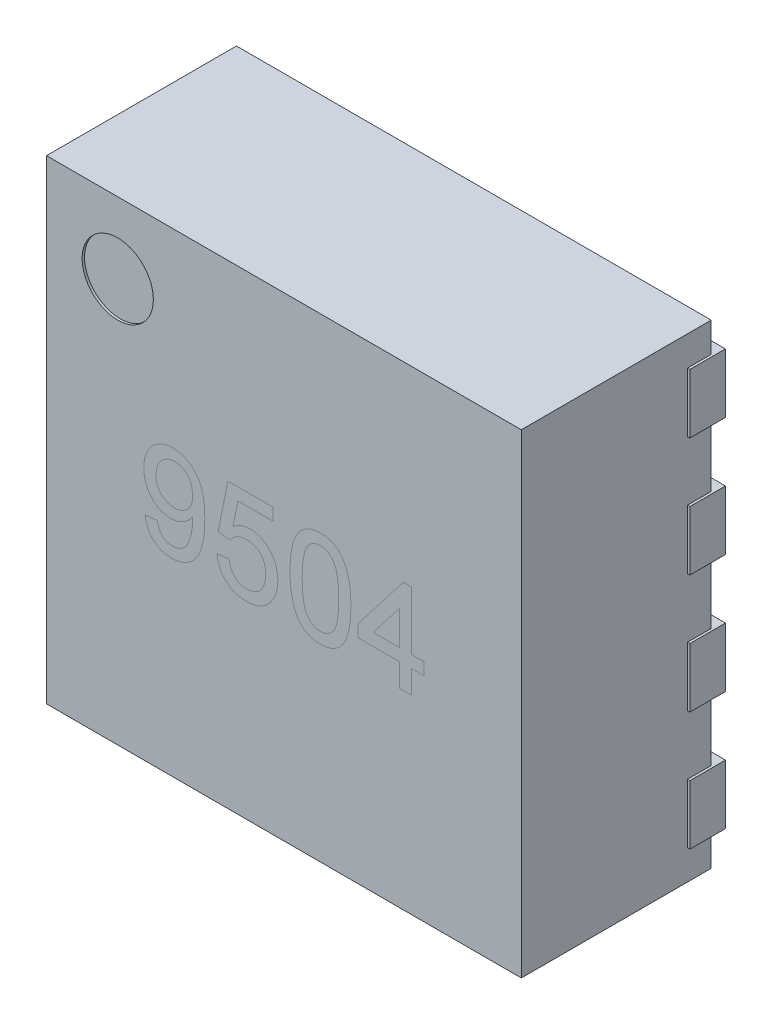
SolidWorks part; units mm, degrees
ref_plane "Спереди" through (0, 0, 0) normal (0, 0, 1) x (1, 0, 0)
ref_plane "Сверху" through (0, 0, 0) normal (0, 1, 0) x (1, 0, 0)
ref_plane "Справа" through (0, 0, 0) normal (1, 0, 0) x (0, 0, -1)
other "Configuration Table"
sketch "Sketch1" plane through (0, 0, 0) normal (0, 0, 1) x (1, 0, 0)
  line L1 (-1, 1) -> (1, 1)
  line L2 (-1, 1) -> (-1, -1)
  line L3 (-1, -1) -> (1, -1)
  line L4 (1, 1) -> (1, -1)
  line L5 (-1, 1) -> (1, -1) construction
  line L6 (-1, -1) -> (1, 1) construction
  point P0 (0, 0)
  dimension "D1" = 2
  dimension "D2" = 2
extrude "Boss-Extrude1" add sketch "Sketch1" along normal blind 0.8
sketch "Sketch3" plane through (0, 0, 0) normal (0, 0, -1) x (-1, 0, 0)
  line L0 (1, 1) -> (1, -1) construction
  line L1 (1.01, 0.875) -> (0.81, 0.875)
  line L2 (1.01, 0.875) -> (1.01, 0.625)
  line L3 (1.01, 0.625) -> (0.81, 0.625)
  line L4 (0.71, 0.775) -> (0.71, 0.725)
  line L5 (0.71, 0.75) -> (1.01, 0.75) construction
  line L6 (1.01, 0.375) -> (1.01, 0.125)
  line L7 (1.01, 0.375) -> (0.81, 0.375)
  line L8 (0.71, 0.275) -> (0.71, 0.225)
  line L9 (1.01, 0.125) -> (0.81, 0.125)
  line L10 (1.01, -0.125) -> (1.01, -0.375)
  line L11 (1.01, -0.125) -> (0.81, -0.125)
  line L12 (0.71, -0.225) -> (0.71, -0.275)
  line L13 (1.01, -0.375) -> (0.81, -0.375)
  line L14 (1.01, -0.625) -> (1.01, -0.875)
  line L15 (1.01, -0.625) -> (0.81, -0.625)
  line L16 (0.71, -0.725) -> (0.71, -0.775)
  line L17 (1.01, -0.875) -> (0.81, -0.875)
  line L18 (0, 1) -> (0, -1) construction
  line L19 (-1, 1) -> (1, 1) construction
  line L20 (1, -1) -> (-1, -1) construction
  line L21 (-0.71, 0.75) -> (-1.01, 0.75) construction
  line L22 (-1.01, -0.875) -> (-0.81, -0.875)
  line L23 (-0.71, -0.725) -> (-0.71, -0.775)
  line L24 (-1.01, -0.625) -> (-0.81, -0.625)
  line L25 (-1.01, -0.625) -> (-1.01, -0.875)
  line L26 (-1.01, -0.375) -> (-0.81, -0.375)
  line L27 (-0.71, -0.225) -> (-0.71, -0.275)
  line L28 (-1.01, -0.125) -> (-0.81, -0.125)
  line L29 (-1.01, -0.125) -> (-1.01, -0.375)
  line L30 (-1.01, 0.125) -> (-0.81, 0.125)
  line L31 (-0.71, 0.275) -> (-0.71, 0.225)
  line L32 (-1.01, 0.375) -> (-0.81, 0.375)
  line L33 (-1.01, 0.375) -> (-1.01, 0.125)
  line L34 (-0.71, 0.775) -> (-0.71, 0.725)
  line L35 (-1.01, 0.625) -> (-0.81, 0.625)
  line L36 (-1.01, 0.875) -> (-1.01, 0.625)
  line L37 (-1.01, 0.875) -> (-0.81, 0.875)
  arc A0 (0.81, 0.625) -> (0.71, 0.725) centre (0.81, 0.725) cw
  arc A1 (0.81, 0.875) -> (0.71, 0.775) centre (0.81, 0.775) ccw
  arc A2 (0.81, 0.375) -> (0.71, 0.275) centre (0.81, 0.275) ccw
  arc A3 (0.81, 0.125) -> (0.71, 0.225) centre (0.81, 0.225) cw
  arc A4 (0.81, -0.125) -> (0.71, -0.225) centre (0.81, -0.225) ccw
  arc A5 (0.81, -0.375) -> (0.71, -0.275) centre (0.81, -0.275) cw
  arc A6 (0.81, -0.625) -> (0.71, -0.725) centre (0.81, -0.725) ccw
  arc A7 (0.81, -0.875) -> (0.71, -0.775) centre (0.81, -0.775) cw
  arc A8 (-0.81, -0.875) -> (-0.71, -0.775) centre (-0.81, -0.775) ccw
  arc A9 (-0.81, -0.625) -> (-0.71, -0.725) centre (-0.81, -0.725) cw
  arc A10 (-0.81, -0.375) -> (-0.71, -0.275) centre (-0.81, -0.275) ccw
  arc A11 (-0.81, -0.125) -> (-0.71, -0.225) centre (-0.81, -0.225) cw
  arc A12 (-0.81, 0.125) -> (-0.71, 0.225) centre (-0.81, 0.225) ccw
  arc A13 (-0.81, 0.375) -> (-0.71, 0.275) centre (-0.81, 0.275) cw
  arc A14 (-0.81, 0.875) -> (-0.71, 0.775) centre (-0.81, 0.775) cw
  arc A15 (-0.81, 0.625) -> (-0.71, 0.725) centre (-0.81, 0.725) ccw
  point P6 (1.01, 0.75)
  dimension "D5" = 0.1
  dimension "D1" = 0.25
  dimension "D2" = 0.01
  dimension "D3" = 0.3
  dimension "D4" = 0.75
  dimension "D6" = 4
extrude "Boss-Extrude2" add sketch "Sketch3" along normal blind 0.05
sketch "Sketch4" plane through (0, 0, 0) normal (0, 0, -1) x (-1, 0, 0)
  line L4 (1.01, 0.875) -> (0.81, 0.875)
  line L5 (0.71, 0.775) -> (0.71, 0.725)
  line L6 (0.81, 0.625) -> (1.01, 0.625)
  line L7 (1.01, 0.625) -> (1.01, 0.875)
  line L8 (1.01, 0.875) -> (0.81, 0.875)
  line L9 (0.71, 0.775) -> (0.71, 0.725)
  line L10 (0.81, 0.625) -> (1.01, 0.625)
  line L11 (1.01, 0.625) -> (1.01, 0.875)
  line L12 (1.01, -0.375) -> (1.01, -0.125)
  line L13 (0.81, -0.375) -> (1.01, -0.375)
  line L14 (0.71, -0.225) -> (0.71, -0.275)
  line L15 (1.01, -0.125) -> (0.81, -0.125)
  line L16 (1.01, -0.375) -> (1.01, -0.125)
  line L17 (0.81, -0.375) -> (1.01, -0.375)
  line L18 (0.71, -0.225) -> (0.71, -0.275)
  line L19 (1.01, -0.125) -> (0.81, -0.125)
  line L20 (1.01, 0.125) -> (1.01, 0.375)
  line L21 (1.01, 0.375) -> (0.81, 0.375)
  line L22 (0.71, 0.275) -> (0.71, 0.225)
  line L23 (0.81, 0.125) -> (1.01, 0.125)
  line L24 (1.01, 0.125) -> (1.01, 0.375)
  line L25 (1.01, 0.375) -> (0.81, 0.375)
  line L26 (0.71, 0.275) -> (0.71, 0.225)
  line L27 (0.81, 0.125) -> (1.01, 0.125)
  line L28 (1.01, -0.875) -> (1.01, -0.625)
  line L29 (1.01, -0.625) -> (0.81, -0.625)
  line L30 (0.71, -0.725) -> (0.71, -0.775)
  line L31 (0.81, -0.875) -> (1.01, -0.875)
  line L32 (1.01, -0.875) -> (1.01, -0.625)
  line L33 (1.01, -0.625) -> (0.81, -0.625)
  line L34 (0.71, -0.725) -> (0.71, -0.775)
  line L35 (0.81, -0.875) -> (1.01, -0.875)
  line L36 (-0.71, 0.725) -> (-0.71, 0.775)
  line L37 (-1.01, 0.625) -> (-0.81, 0.625)
  line L38 (-1.01, 0.875) -> (-1.01, 0.625)
  line L39 (-0.81, 0.875) -> (-1.01, 0.875)
  line L40 (-0.71, 0.725) -> (-0.71, 0.775)
  line L41 (-1.01, 0.625) -> (-0.81, 0.625)
  line L42 (-1.01, 0.875) -> (-1.01, 0.625)
  line L43 (-0.81, 0.875) -> (-1.01, 0.875)
  line L44 (-1.01, 0.125) -> (-0.81, 0.125)
  line L45 (-0.71, 0.225) -> (-0.71, 0.275)
  line L46 (-0.81, 0.375) -> (-1.01, 0.375)
  line L47 (-1.01, 0.375) -> (-1.01, 0.125)
  line L48 (-1.01, 0.125) -> (-0.81, 0.125)
  line L49 (-0.71, 0.225) -> (-0.71, 0.275)
  line L50 (-0.81, 0.375) -> (-1.01, 0.375)
  line L51 (-1.01, 0.375) -> (-1.01, 0.125)
  line L52 (-1.01, -0.375) -> (-0.81, -0.375)
  line L53 (-0.71, -0.275) -> (-0.71, -0.225)
  line L54 (-0.81, -0.125) -> (-1.01, -0.125)
  line L55 (-1.01, -0.125) -> (-1.01, -0.375)
  line L56 (-1.01, -0.375) -> (-0.81, -0.375)
  line L57 (-0.71, -0.275) -> (-0.71, -0.225)
  line L58 (-0.81, -0.125) -> (-1.01, -0.125)
  line L59 (-1.01, -0.125) -> (-1.01, -0.375)
  line L60 (-1.01, -0.875) -> (-0.81, -0.875)
  line L61 (-0.71, -0.775) -> (-0.71, -0.725)
  line L62 (-0.81, -0.625) -> (-1.01, -0.625)
  line L63 (-1.01, -0.625) -> (-1.01, -0.875)
  line L64 (-1.01, -0.875) -> (-0.81, -0.875)
  line L65 (-0.71, -0.775) -> (-0.71, -0.725)
  line L66 (-0.81, -0.625) -> (-1.01, -0.625)
  line L67 (-1.01, -0.625) -> (-1.01, -0.875)
  arc A2 (0.81, 0.875) -> (0.71, 0.775) centre (0.81, 0.775) ccw
  arc A3 (0.71, 0.725) -> (0.81, 0.625) centre (0.81, 0.725) ccw
  arc A4 (0.81, 0.875) -> (0.71, 0.775) centre (0.81, 0.775) ccw
  arc A5 (0.71, 0.725) -> (0.81, 0.625) centre (0.81, 0.725) ccw
  arc A6 (0.71, -0.275) -> (0.81, -0.375) centre (0.81, -0.275) ccw
  arc A7 (0.81, -0.125) -> (0.71, -0.225) centre (0.81, -0.225) ccw
  arc A8 (0.71, -0.275) -> (0.81, -0.375) centre (0.81, -0.275) ccw
  arc A9 (0.81, -0.125) -> (0.71, -0.225) centre (0.81, -0.225) ccw
  arc A10 (0.81, 0.375) -> (0.71, 0.275) centre (0.81, 0.275) ccw
  arc A11 (0.71, 0.225) -> (0.81, 0.125) centre (0.81, 0.225) ccw
  arc A12 (0.81, 0.375) -> (0.71, 0.275) centre (0.81, 0.275) ccw
  arc A13 (0.71, 0.225) -> (0.81, 0.125) centre (0.81, 0.225) ccw
  arc A14 (0.81, -0.625) -> (0.71, -0.725) centre (0.81, -0.725) ccw
  arc A15 (0.71, -0.775) -> (0.81, -0.875) centre (0.81, -0.775) ccw
  arc A16 (0.81, -0.625) -> (0.71, -0.725) centre (0.81, -0.725) ccw
  arc A17 (0.71, -0.775) -> (0.81, -0.875) centre (0.81, -0.775) ccw
  arc A18 (-0.81, 0.625) -> (-0.71, 0.725) centre (-0.81, 0.725) ccw
  arc A19 (-0.71, 0.775) -> (-0.81, 0.875) centre (-0.81, 0.775) ccw
  arc A20 (-0.81, 0.625) -> (-0.71, 0.725) centre (-0.81, 0.725) ccw
  arc A21 (-0.71, 0.775) -> (-0.81, 0.875) centre (-0.81, 0.775) ccw
  arc A22 (-0.81, 0.125) -> (-0.71, 0.225) centre (-0.81, 0.225) ccw
  arc A23 (-0.71, 0.275) -> (-0.81, 0.375) centre (-0.81, 0.275) ccw
  arc A24 (-0.81, 0.125) -> (-0.71, 0.225) centre (-0.81, 0.225) ccw
  arc A25 (-0.71, 0.275) -> (-0.81, 0.375) centre (-0.81, 0.275) ccw
  arc A26 (-0.81, -0.375) -> (-0.71, -0.275) centre (-0.81, -0.275) ccw
  arc A27 (-0.71, -0.225) -> (-0.81, -0.125) centre (-0.81, -0.225) ccw
  arc A28 (-0.81, -0.375) -> (-0.71, -0.275) centre (-0.81, -0.275) ccw
  arc A29 (-0.71, -0.225) -> (-0.81, -0.125) centre (-0.81, -0.225) ccw
  arc A30 (-0.81, -0.875) -> (-0.71, -0.775) centre (-0.81, -0.775) ccw
  arc A31 (-0.71, -0.725) -> (-0.81, -0.625) centre (-0.81, -0.725) ccw
  arc A32 (-0.81, -0.875) -> (-0.71, -0.775) centre (-0.81, -0.775) ccw
  arc A33 (-0.71, -0.725) -> (-0.81, -0.625) centre (-0.81, -0.725) ccw
  dimension "D1" = 0
  dimension "D2" = 0
  dimension "D3" = 0
  dimension "D4" = 0
  dimension "D5" = 0
  dimension "D6" = 0
  dimension "D7" = 0
  dimension "D8" = 0
extrude "Boss-Extrude3" add sketch "Sketch4" against normal blind 0.1
sketch "Sketch5" plane through (0, 0, 0.8) normal (0, 0, 1) x (1, 0, 0)
  line L0 (-1, 1) -> (1, -1) construction
  line L1 (1, 1) -> (-1, 1) construction
  circle A0 centre (-0.7, 0.7) radius 0.15
  dimension "D1" = 0.3
  dimension "D2" = 0.3
extrude "Cut-Extrude1" cut sketch "Sketch5" against normal blind 0.01
sketch "Sketch6" plane through (0, 0, 0.8) normal (0, 0, 1) x (1, 0, 0)
  line L0 (-1, -0.2) -> (1, -0.2) construction
  line L1 (-1, 1) -> (-1, -1) construction
  line L2 (1, -1) -> (1, 1) construction
  line L3 (-1, -1) -> (1, -1) construction
  text T0 "9504" height 0.4
  dimension "D1" = 0.8
wrap "Wrap1" sketch "Sketch6" wrap type scribe source sketch "Sketch6"
